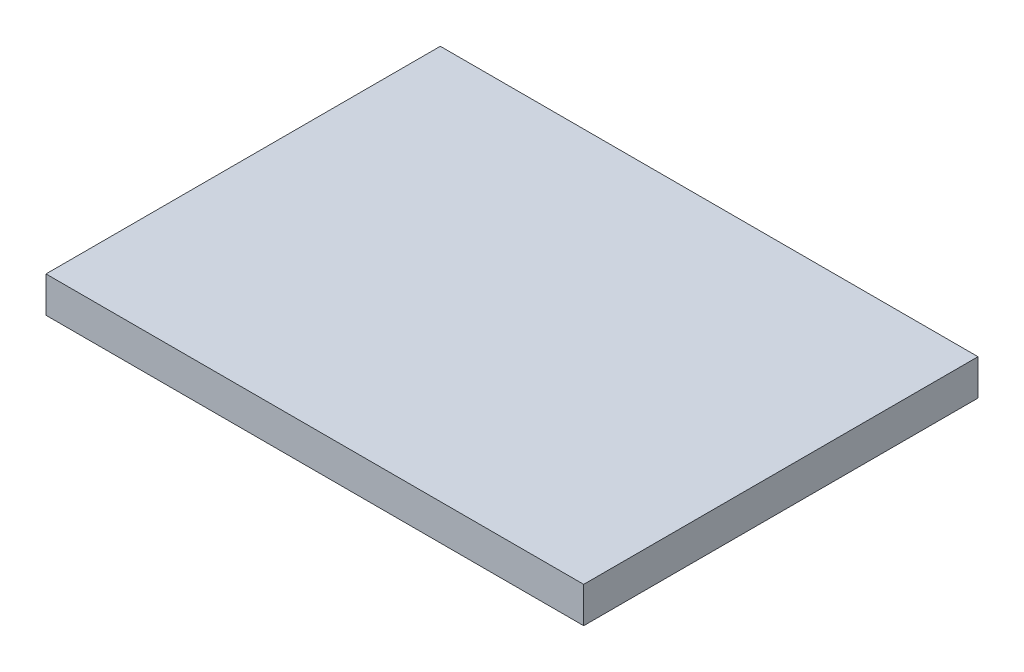
SolidWorks part; units mm, degrees
ref_plane "Front Plane" through (0, 0, 0) normal (0, 0, 1) x (1, 0, 0)
ref_plane "Top Plane" through (0, 0, 0) normal (0, 1, 0) x (1, 0, 0)
ref_plane "Right Plane" through (0, 0, 0) normal (1, 0, 0) x (0, 0, -1)
sketch "Sketch1" plane through (0, 0, 0) normal (0, 1, 0) x (1, 0, 0)
  line L1 (0, -27.5) -> (75, -27.5)
  line L2 (0, -27.5) -> (0, 27.5)
  line L3 (0, 27.5) -> (75, 27.5)
  line L4 (75, -27.5) -> (75, 27.5)
  point P5 (0, 0)
  dimension "D1" = 75
  dimension "D2" = 55
extrude "Boss-Extrude1" add sketch "Sketch1" along normal blind 5
